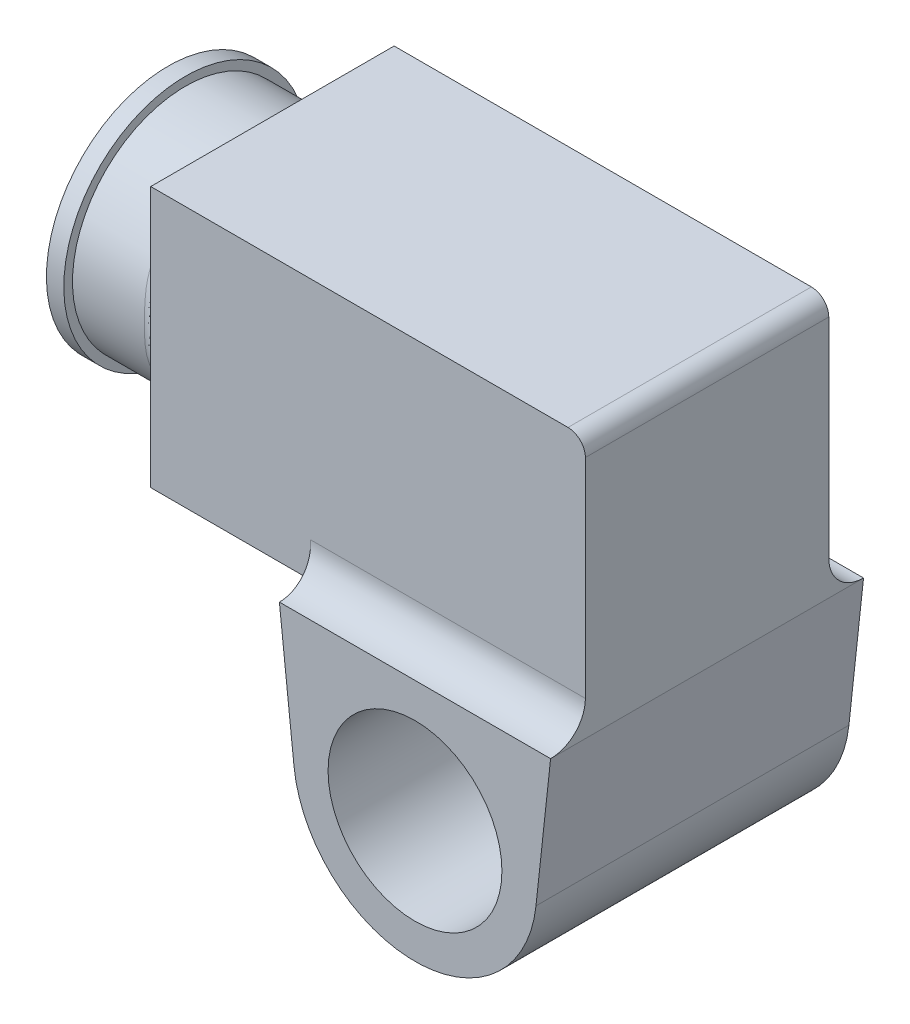
SolidWorks part; units mm, degrees
material "普通碳钢"
ref_plane "Front Plane" through (0, 0, 0) normal (0, 0, 1) x (1, 0, 0)
ref_plane "Top Plane" through (0, 0, 0) normal (0, 1, 0) x (1, 0, 0)
ref_plane "Right Plane" through (0, 0, 0) normal (1, 0, 0) x (0, 0, -1)
sketch "Sketch1" plane through (0, 0, 0) normal (0, 0, 1) x (1, 0, 0)
  line L0 (78, 70) -> (-172, 70)
  line L1 (0, 0) -> (0, 70) construction
  line L2 (69.5921, -7.5455) -> (78, 70)
  line L3 (-69.5921, -7.5455) -> (-78, 70)
  line L4 (78, 70) -> (78, 220)
  line L5 (78, 220) -> (-172, 220)
  line L6 (-172, 220) -> (-172, 70)
  circle A0 centre (0, 0) radius 50
  arc A1 (-69.5921, -7.5455) -> (69.5921, -7.5455) centre (0, 0) ccw
  dimension "D1" = 100
  dimension "D2" = 70
  dimension "D3" = 70
  dimension "D4" = 156
  dimension "D5" = 250
  dimension "D6" = 150
extrude "Boss-Extrude1" add sketch "Sketch1" along normal mid plane 180 contours A0 L0 L3 A1 L2 region at (71.7122, 31.4532, 0)
extrude "Boss-Extrude2" add sketch "Sketch1<3>" along normal mid plane 140 contours L4 L5 L6 L0
sketch "Sketch1<3>" plane through (0, 0, 0) normal (0, 0, 1) x (1, 0, 0) same geometry as "Sketch1"
fillet "Fillet1" radius 20 2 edges at (0, 70, -70) (0, 70, 70)
fillet "Fillet2" radius 10 1 edges at (78, 220, 0)
sketch "Sketch2" plane through (-172, 0, 0) normal (-1, 0, 0) x (0, 0, 1)
  line L0 (0, 220) -> (0, 70) construction
  line L1 (70, 220) -> (-70, 220) construction
  line L2 (70, 70) -> (-70, 70) construction
  line L3 (-70, 145) -> (70, 145) construction
  line L4 (-70, 220) -> (-70, 70) construction
  line L5 (70, 220) -> (70, 70) construction
  circle A0 centre (0, 145) radius 65
  point P15 (0, 145)
  dimension "D1" = 130
extrude "Boss-Extrude3" add sketch "Sketch2" along normal blind 50
sketch "Sketch3" plane through (-222, 0, 0) normal (-1, 0, 0) x (0, 0, 1)
  circle A0 centre (0, 145) radius 70
  circle A1 centre (0, 145) radius 65 construction
  dimension "D1" = 140
extrude "Boss-Extrude4" add sketch "Sketch3" along normal blind 10
sketch "Sketch4" plane through (-232, 0, 0) normal (-1, 0, 0) x (0, 0, 1)
  circle A0 centre (0, 145) radius 40
  dimension "D1" = 80
extrude "Cut-Extrude1" cut sketch "Sketch4" against normal blind 40
fillet "Fillet3" radius 10 1 edges at (-172, 210, 0)
scale "缩放比例1" scale about centroid uniform scaling yes scale factor 0.135065
